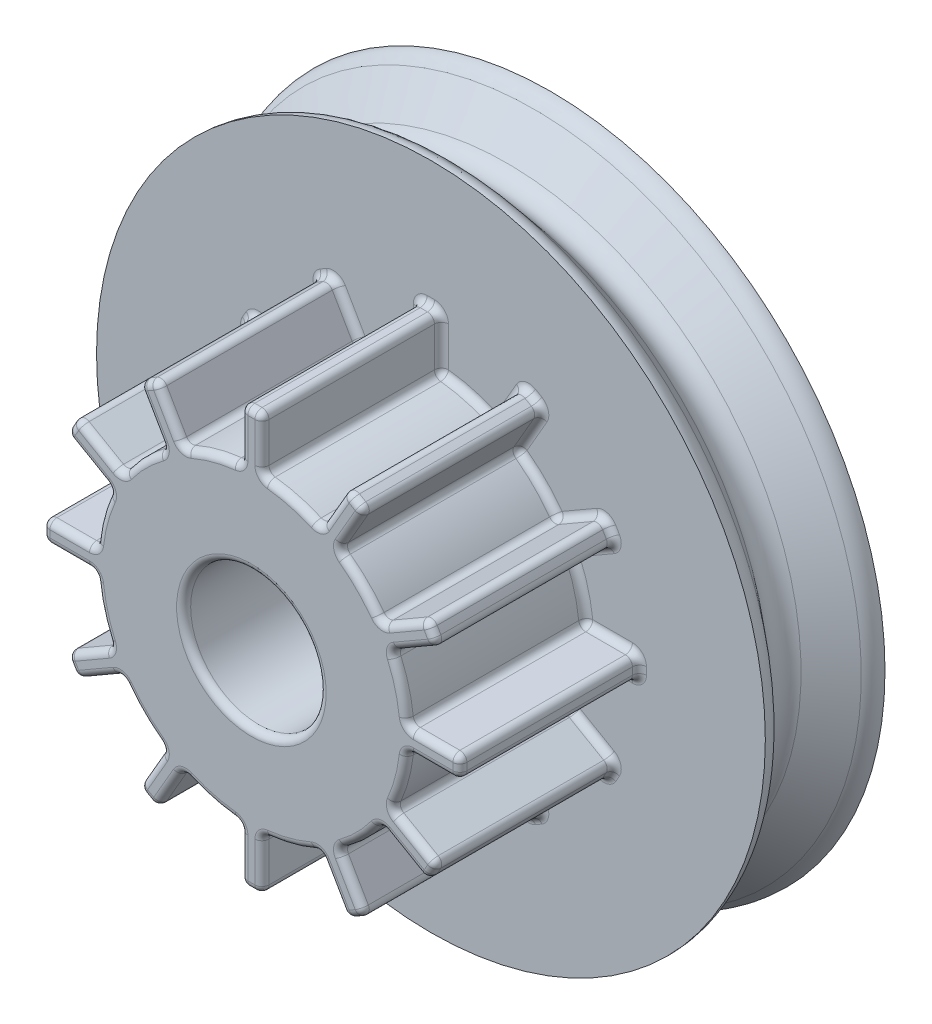
SolidWorks part; units mm, degrees
note: '?' marks a value the reader was unsure of.
ref_plane "Front Plane" through (0, 0, 0) normal (0, 0, 1) x (1, 0, 0)
ref_plane "Top Plane" through (0, 0, 0) normal (0, 1, 0) x (1, 0, 0)
ref_plane "Right Plane" through (0, 0, 0) normal (1, 0, 0) x (0, 0, -1)
sketch "Sketch2" plane through (0, 0, 0) normal (1, 0, 0) x (0, 0, -1)
  line L0 (0, 3.85) -> (-17, 3.85)
  line L1 (-17, 3.85) -> (-17, 11.85)
  line L2 (-17, 11.85) -> (-6.8, 11.85)
  line L3 (-6.8, 11.85) -> (-6.8, 19)
  line L4 (-5.8807, 18.5713) -> (-4.3193, 16.7104)
  line L5 (-2.4807, 16.7104) -> (-0.9193, 18.5713)
  line L6 (0, 19) -> (0, 3.85)
  line L7 (-17, 25) -> (-6.8, 25) construction
  line L8 (0, 0) -> (-45.1775, 0) construction
  arc A0 (-6.8, 19) -> (-5.8807, 18.5713) centre (-6.8, 17.8) cw
  arc A1 (-4.3193, 16.7104) -> (-2.4807, 16.7104) centre (-3.4, 17.4818) ccw
  arc A2 (-0.9193, 18.5713) -> (0, 19) centre (0, 17.8) cw
  dimension "D1" = 17
  dimension "D8" = 1.2
  dimension "D2" = 3.85
  dimension "D3" = 25
  dimension "D4" = 40
  dimension "D5" = 6.8
  dimension "D6" = 8
  dimension "D7" = 6
revolve "Revolve1" add sketch "Sketch2" angle 360 about L8
sketch "Sketch3" plane through (0, 0, 17) normal (0, 0, 1) x (1, 0, 0)
  line L0 (0, 19) -> (0, 0) construction
  line L1 (0, 0) -> (9.5, 16.4545) construction
  line L2 (0.6, 18.9905) -> (0.6, 2.2392)
  line L3 (0.6, 2.2392) -> (8.9756, 16.7463)
  circle A0 centre (0, 0) radius 19 construction
  arc A1 (8.9756, 16.7463) -> (0.6, 18.9905) centre (0.6, 2.2392) ccw
  arc A2 (0.6, 8.8296) -> (3.8952, 7.9467) centre (0, 0) cw
  circle A3 centre (0, 0) radius 11.85 construction
  circle A4 centre (0, 0) radius 3.85 construction
  circle M6 centre (0, 0) radius 11.85
  dimension "D2" = 1.2
  dimension "D4" = 5
  dimension "D1" = 30
  dimension "D3" = 1.2
extrude "Cut-Extrude1" cut sketch "Sketch3" against normal up to surface (10.2 mm away) contours L2 A2 L3 M6 | L3 A1 L2 M6
ref_axis "Axis1" through (0, 0, 17) along (0, 0, -1)?
pattern_circular "CirPattern1" count 12 over 360 about axis through (0, 0, 0) along (0, 0, 1) of "Cut-Extrude1"
fillet "Fillet2" radius 0.4 146 edges at (-10.3322, -0.6, 6.8) (-10.3322, -0.6, 17) (-10.3322, 0.6, 17) (-10.3322, 0.6, 6.8) (-8.648, -5.6857, 6.8) (-8.648, -5.6857, 17) (-9.248, -4.6465, 17) (-9.248, -4.6465, 6.8) (-4.6465, -9.248, 6.8) (-4.6465, -9.248, 17) (-5.6857, -8.648, 17) (-5.6857, -8.648, 6.8) (0.6, -10.3322, 6.8) (0.6, -10.3322, 17) (-0.6, -10.3322, 17) (-0.6, -10.3322, 6.8) (5.6857, -8.648, 6.8) (5.6857, -8.648, 17) (4.6465, -9.248, 17) (4.6465, -9.248, 6.8) (9.248, -4.6465, 6.8) (9.248, -4.6465, 17) (8.648, -5.6857, 17) (8.648, -5.6857, 6.8) (10.3322, 0.6, 6.8) (10.3322, 0.6, 17) (10.3322, -0.6, 17) (10.3322, -0.6, 6.8) (8.648, 5.6857, 6.8) (8.648, 5.6857, 17) (9.248, 4.6465, 17) (9.248, 4.6465, 6.8) (4.6465, 9.248, 6.8) (4.6465, 9.248, 17) (5.6857, 8.648, 17) (5.6857, 8.648, 6.8) (-0.6, 10.3322, 6.8) (-0.6, 10.3322, 17) (0.6, 10.3322, 17) (0.6, 10.3322, 6.8) (-5.6857, 8.648, 6.8) (-5.6857, 8.648, 17) (-4.6465, 9.248, 17) (-4.6465, 9.248, 6.8) (-9.248, 4.6465, 6.8) (-9.248, 4.6465, 17) (-8.648, 5.6857, 17) (-8.648, 5.6857, 6.8) (-8.8296, -0.6, 11.9) (-7.9467, -3.8952, 11.9) (-8.5484, -2.2905, 6.8) (-8.5484, -2.2905, 17) (-7.3467, -4.9344, 11.9) (-4.9344, -7.3467, 11.9) (-6.2579, -6.2579, 6.8) (-6.2579, -6.2579, 17) (-3.8952, -7.9467, 11.9) (-0.6, -8.8296, 11.9) (-2.2905, -8.5484, 6.8) (-2.2905, -8.5484, 17) (0.6, -8.8296, 11.9) (3.8952, -7.9467, 11.9) (2.2905, -8.5484, 6.8) (2.2905, -8.5484, 17) (4.9344, -7.3467, 11.9) (7.3467, -4.9344, 11.9) (6.2579, -6.2579, 6.8) (6.2579, -6.2579, 17) (7.9467, -3.8952, 11.9) (8.8296, -0.6, 11.9) (8.5484, -2.2905, 6.8) (8.5484, -2.2905, 17) (8.8296, 0.6, 11.9) (7.9467, 3.8952, 11.9) (8.5484, 2.2905, 6.8) (8.5484, 2.2905, 17) (7.3467, 4.9344, 11.9) (4.9344, 7.3467, 11.9) (6.2579, 6.2579, 6.8) (6.2579, 6.2579, 17) (3.8952, 7.9467, 11.9) (0.6, 8.8296, 11.9) (2.2905, 8.5484, 6.8) (2.2905, 8.5484, 17) (-0.6, 8.8296, 11.9) (-3.8952, 7.9467, 11.9) (-2.2905, 8.5484, 6.8) (-2.2905, 8.5484, 17) (-4.9344, 7.3467, 11.9) (-7.3467, 4.9344, 11.9) (-6.2579, 6.2579, 6.8) (-6.2579, 6.2579, 17) (-7.9467, 3.8952, 11.9) (-8.8296, 0.6, 11.9) (-8.5484, 2.2905, 6.8) (-8.5484, 2.2905, 17) (-11.8348, -0.6, 11.9) (-11.85, 0, 6.8) (-11.8348, 0.6, 11.9) (-10.2624, -5.925, 6.8) (-10.5492, -5.3978, 11.9) (-9.9492, -6.437, 11.9) (-5.3978, -10.5492, 11.9) (-5.925, -10.2624, 6.8) (-6.437, -9.9492, 11.9) (0.6, -11.8348, 11.9) (0, -11.85, 6.8) (-0.6, -11.8348, 11.9) (6.437, -9.9492, 11.9) (5.925, -10.2624, 6.8) (5.3978, -10.5492, 11.9) (10.2624, -5.925, 6.8) (9.9492, -6.437, 11.9) (10.5492, -5.3978, 11.9) (11.85, 0, 6.8) (11.8348, -0.6, 11.9) (11.8348, 0.6, 11.9) (9.9492, 6.437, 11.9) (10.2624, 5.925, 6.8) (10.5492, 5.3978, 11.9) (5.3978, 10.5492, 11.9) (5.925, 10.2624, 6.8) (6.437, 9.9492, 11.9) (0, 11.85, 6.8) (0.6, 11.8348, 11.9) (-0.6, 11.8348, 11.9) (-6.437, 9.9492, 11.9) (-5.925, 10.2624, 6.8) (-5.3978, 10.5492, 11.9) (-5.925, 10.2624, 17) (0, 11.85, 17) (5.925, 10.2624, 17) (10.2624, 5.925, 17) (11.85, 0, 17) (10.2624, -5.925, 17) (5.925, -10.2624, 17) (0, -11.85, 17) (-5.925, -10.2624, 17) (-10.2624, -5.925, 17) (-11.85, 0, 17) (-3.85, 0, 17) (-10.2624, 5.925, 6.8) (-9.9492, 6.437, 11.9) (-10.2624, 5.925, 17) (-10.5492, 5.3978, 11.9) (-3.85, 0, 0)
sketch "Sketch4" plane through (0, 0, 0) normal (0, 0, -1) x (-1, 0, 0)
  circle A0 centre (0, 0) radius 14
  circle A1 centre (0, 0) radius 7
  dimension "D1" = 14
  dimension "D2" = 28
extrude "Cut-Extrude2" cut sketch "Sketch4" against normal offset from surface (4.4 mm away) 2.4
fillet "Fillet3" radius 1.6 4 edges at (-14, 0, 0) (-7, 0, 0) (7, 0, 4.4) (14, 0, 4.4)
